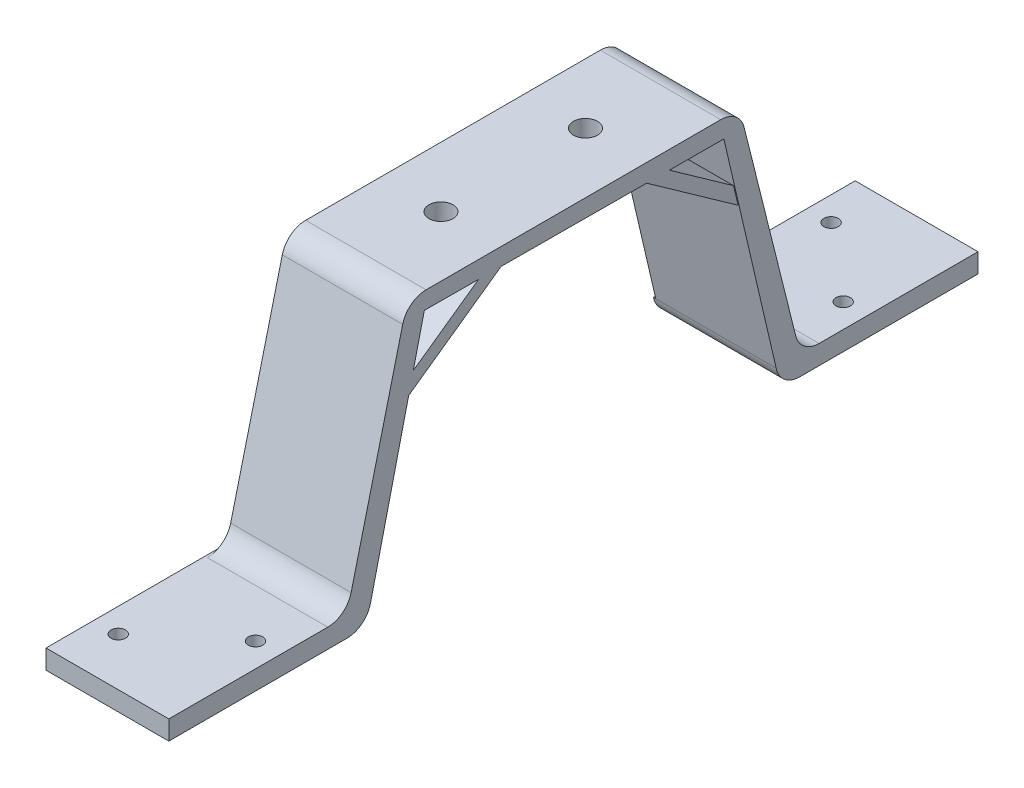
SolidWorks part; units mm, degrees
ref_plane "Alzado" through (0, 0, 0) normal (0, 0, 1) x (1, 0, 0)
ref_plane "Planta" through (0, 0, 0) normal (0, 1, 0) x (1, 0, 0)
ref_plane "Vista lateral" through (0, 0, 0) normal (1, 0, 0) x (0, 0, -1)
sketch "Croquis1" plane through (0, 0, 0) normal (1, 0, 0) x (0, 0, -1)
  line L1 (0, 0) -> (-168, 0)
  line L2 (0, 0) -> (0, 4)
  line L3 (0, 4) -> (-168, 4)
  line L4 (-168, 0) -> (-168, 4)
  dimension "D1" = 4
  dimension "D2" = 168
extrude "Saliente-Extruir1" add sketch "Croquis1" along normal blind 25.5
sketch "Croquis2" plane through (25.5, 0, 0) normal (1, 0, 0) x (0, 0, -1)
  line L0 (-131.1, 4) -> (-118.4963, 54.4494)
  line L1 (0, 4) -> (-168, 4) construction
  line L2 (-168, 4) -> (-168, 0) construction
  line L3 (-84, 4) -> (-84, 0) construction
  line L4 (-168, 0) -> (0, 0) construction
  line L5 (-36.9, 4) -> (-49.5037, 54.4494)
  line L6 (-118.4963, 54.4494) -> (-49.5037, 54.4494)
  line L7 (-131.1, 4) -> (-126.1, 4)
  line L8 (-126.1, 4) -> (-114.9508, 50.9239)
  line L9 (-114.9508, 50.9239) -> (-52.7648, 50.6593)
  line L10 (-52.7648, 50.6593) -> (-41.9, 4)
  line L11 (-41.9, 4) -> (-36.9, 4)
  point P12 (-114.9508, 50.9239)
  point P13 (-52.7648, 50.6593)
  point P14 (-126.1, 4)
  point P15 (-41.9, 4)
  dimension "D1" = 36.9
  dimension "D2" = 49.5037
  dimension "D3" = 52
  dimension "D4" = 5
  dimension "D5" = 5
  dimension "D6" = 5
  dimension "D7" = 5
extrude "Saliente-Extruir2" add sketch "Croquis2" against normal blind 25 contours L11 L5 L6 L0 L7 L8 L9 L10
sketch "Croquis17" plane through (25.5, 0, 0) normal (1, 0, 0) x (0, 0, -1)
  line L0 (-103.6794, 50.8759) -> (-117.2489, 41.2518)
  line L1 (-114.9508, 50.9239) -> (-52.7648, 50.6593) construction
  line L2 (-126.1, 4) -> (-114.9508, 50.9239) construction
  line L3 (-117.2489, 41.2518) -> (-118.1993, 37.2518)
  line L4 (-118.1993, 37.2518) -> (-99.0179, 50.8561)
  line L5 (-99.0179, 50.8561) -> (-103.6794, 50.8759)
  line L6 (-84, 54.4494) -> (-84, 2.7764) construction
  line L7 (-118.4963, 54.4494) -> (-49.5037, 54.4494) construction
  line L8 (-49.8007, 37.2518) -> (-68.9821, 50.8561)
  line L9 (-50.7511, 41.2518) -> (-49.8007, 37.2518)
  line L10 (-64.3206, 50.8759) -> (-50.7511, 41.2518)
  line L11 (-68.9821, 50.8561) -> (-64.3206, 50.8759)
  dimension "D1" = 4
extrude "Saliente-Extruir3" add sketch "Croquis17" against normal blind 25
sketch "Croquis19" plane through (25.5, 0, 0) normal (1, 0, 0) x (0, 0, -1)
  line L0 (-126.1, 4) -> (-41.9, 4)
  line L1 (-126.1, 4) -> (-126.1, -3.0749)
  line L2 (-41.9, 4) -> (-41.9, -3.0749)
  line L3 (-126.1, -3.0749) -> (-41.9, -3.0749)
  point P0 (-126.1, -3.0749)
extrude "Cortar-Extruir1" cut sketch "Croquis19" against normal blind 26
fillet "Redondeo1" radius 5 1 edges at (12.75, 0, 126.1)
fillet "Redondeo2" radius 5 5 edges at (13, 54.4494, 49.5037) (13, 54.4494, 118.4963) (12.75, 0, 41.9) (13, 4, 36.9) (13, 4, 131.1)
sketch "Croquis20" plane through (0, 54.4494, 0) normal (0, 1, 0) x (1, 0, 0)
  line L0 (25.5, 0) -> (0, 0) construction
  line L1 (0, 0) -> (0, -41.9) construction
  line L2 (25.5, 0) -> (25.5, -32.9955) construction
  line L3 (0.5, -32.9955) -> (25.5, -32.9955) construction
  line L4 (0.5, -84) -> (25.5, -84) construction
  line L5 (0.5, -114.5918) -> (0.5, -53.4082) construction
  line L6 (25.5, -114.5918) -> (25.5, -53.4082) construction
  circle A0 centre (5, -10) radius 1.5
  circle A1 centre (20.5, -22.9955) radius 1.5
  circle A2 centre (20.5, -145.0045) radius 1.5
  circle A3 centre (5, -158) radius 1.5
  dimension "D5" = 3
  dimension "D6" = 3
  dimension "D1" = 10
  dimension "D2" = 5
  dimension "D3" = 5
  dimension "D4" = 10
extrude "Cortar-Extruir2" cut sketch "Croquis20" against normal blind 100
sketch "Croquis21" plane through (0, 54.4494, 0) normal (0, 1, 0) x (1, 0, 0)
  line L0 (13, -53.4082) -> (13, -114.5918) construction
  line L1 (25.5, -53.4082) -> (0.5, -53.4082) construction
  line L2 (0.5, -114.5918) -> (25.5, -114.5918) construction
  line L3 (0.5, -84) -> (25.5, -84) construction
  line L4 (0.5, -114.5918) -> (0.5, -53.4082) construction
  line L5 (25.5, -114.5918) -> (25.5, -53.4082) construction
  circle A0 centre (13, -69) radius 2.5
  circle A1 centre (13, -99) radius 2.5
  dimension "D1" = 5
  dimension "D2" = 15
extrude "Cortar-Extruir3" cut sketch "Croquis21" against normal blind 100
